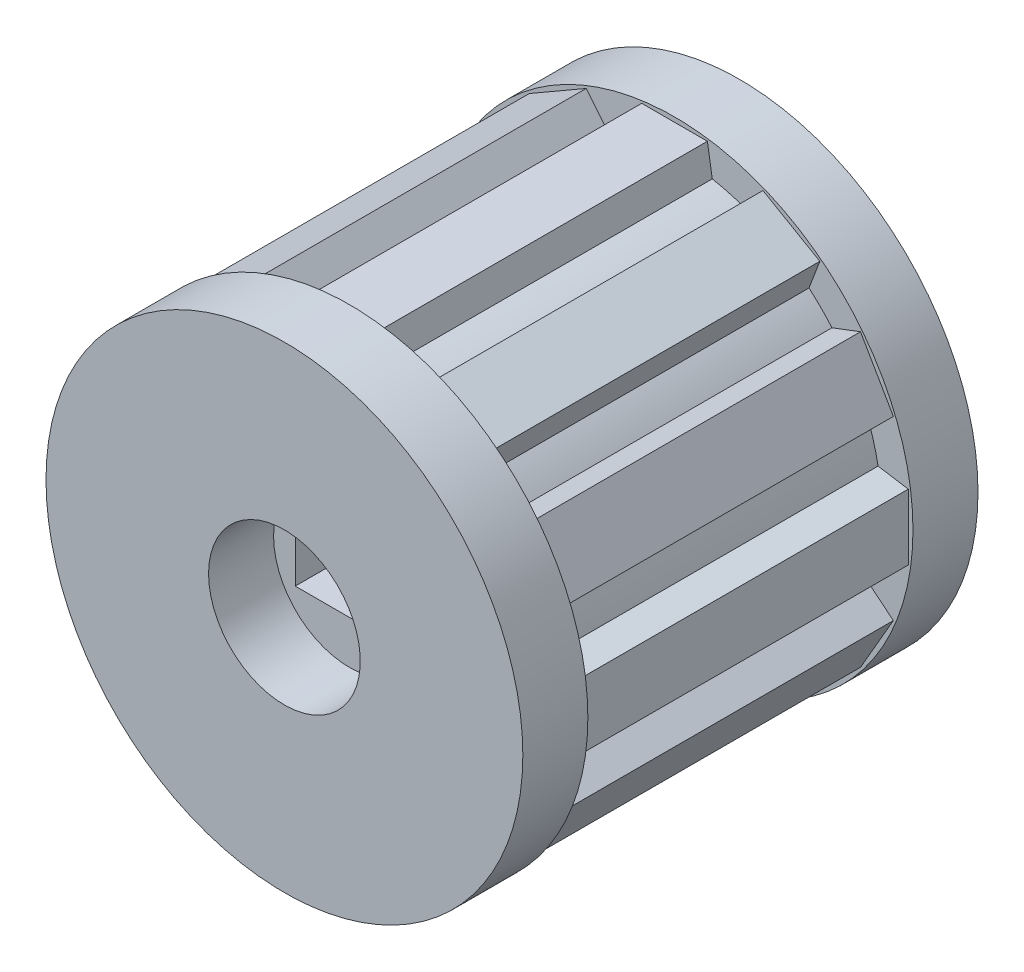
SolidWorks part; units mm, degrees
ref_plane "Plan de face" through (0, 0, 0) normal (0, 0, 1) x (1, 0, 0)
ref_plane "Plan de dessus" through (0, 0, 0) normal (0, 1, 0) x (1, 0, 0)
ref_plane "Plan de droite" through (0, 0, 0) normal (1, 0, 0) x (0, 0, -1)
sketch "Esquisse1" plane through (0, 0, 0) normal (0, 0, 1) x (1, 0, 0)
  line L0 (-2.5, 1.5) -> (2.5, 1.5)
  line L1 (-2.5, 1.5) -> (-2.5, -1.5)
  line L2 (-2.5, -1.5) -> (2.5, -1.5)
  line L3 (2.5, 1.5) -> (2.5, -1.5)
  circle A0 centre (0, 0) radius 11
  circle A1 centre (0, 0) radius 3.5
  point P7 (0, 1.5)
  point P8 (-2.5, 0)
  dimension "D1" = 22
  dimension "D2" = 5
  dimension "D3" = 3
extrude "Boss.-Extru.1" add sketch "Esquisse1" along normal blind 21 contours A0 A1 region at (-10.6889, 0, 0)
sketch "Esquisse2" plane through (0, 0, 0) normal (1, 0, 0) x (0, 0, -1)
  line L0 (0, 0) -> (-44, 0) construction
  line L1 (0, 0) -> (-22, 0)
  line L2 (-22, 0) -> (-22, 3.5)
  line L4 (-22, 3.5) -> (0, 3.5)
  line L6 (0, 3.5) -> (0, 0)
  dimension "D1" = 0
  dimension "D2" = 3.5
revolve "Enlèvement de matière-Révolution1" [suppressed] cut sketch "Esquisse2" angle 360 about L0
ref_plane "Plan1" through (0, 0, 3) normal (0, 0, -1) x (-1, 0, 0)
sketch "Esquisse3" plane through (0, 0, 3) normal (0, 0, -1) x (-1, 0, 0)
  circle A0 centre (0, 0) radius 9.55
  circle A1 centre (0, 0) radius 28.5
  dimension "D1" = 19.1
extrude "Enlèv. mat.-Extru.1" cut sketch "Esquisse3" against normal blind 15
sketch "Esquisse5" plane through (0, 0, 3) normal (0, 0, 1) x (1, 0, 0)
  line L0 (0, 0) -> (0, 38.7923) construction
  line L1 (0, 38.7923) -> (-15.821, 9.55) construction
  line L2 (-15.821, 9.55) -> (15.2424, 9.55) construction
  line L3 (0, 0) -> (-3.1054, 16.7555) construction
  line L7 (-1.7403, 9.3901) -> (-1.5153, 10.7822)
  line L8 (-1.5153, 10.7822) -> (1.5153, 10.7822)
  line L9 (0, 0) -> (3.1059, 16.758) construction
  line L10 (1.5153, 10.7822) -> (1.7403, 9.3901)
  line L11 (0, 0) -> (-1.8224, 12.9667) construction
  line L12 (0, 0) -> (1.8058, 12.8491) construction
  circle A0 centre (0, 0) radius 9.55 construction
  arc A1 (-1.7403, 9.3901) -> (1.7403, 9.3901) centre (0, 0) cw
  dimension "D5" = 10.5
  dimension "D6" = 10.5
  dimension "D7" = 9.55
  dimension "D1" = 3.0307
  dimension "D2" = 8
  dimension "D3" = 8
  dimension "D4" = 1.3921
extrude "Boss.-Extru.2" add sketch "Esquisse5" along normal up to surface (15 mm away) up to face at (-9.55, 0, 18)
pattern_circular "Répétition circulaire1" count 12 over 360 about axis through (0, 0, 3) along (0, 0, -1) of "Boss.-Extru.2"
extrude "Boss-Extrude1" add sketch "Esquisse1<3>" along normal mid plane 15 from offset 10.5 contours A1 L0 L3 L2 L1 region at (-3.401, 0, 0)
sketch "Esquisse1<3>" plane through (0, 0, 0) normal (0, 0, 1) x (1, 0, 0) same geometry as "Esquisse1"
